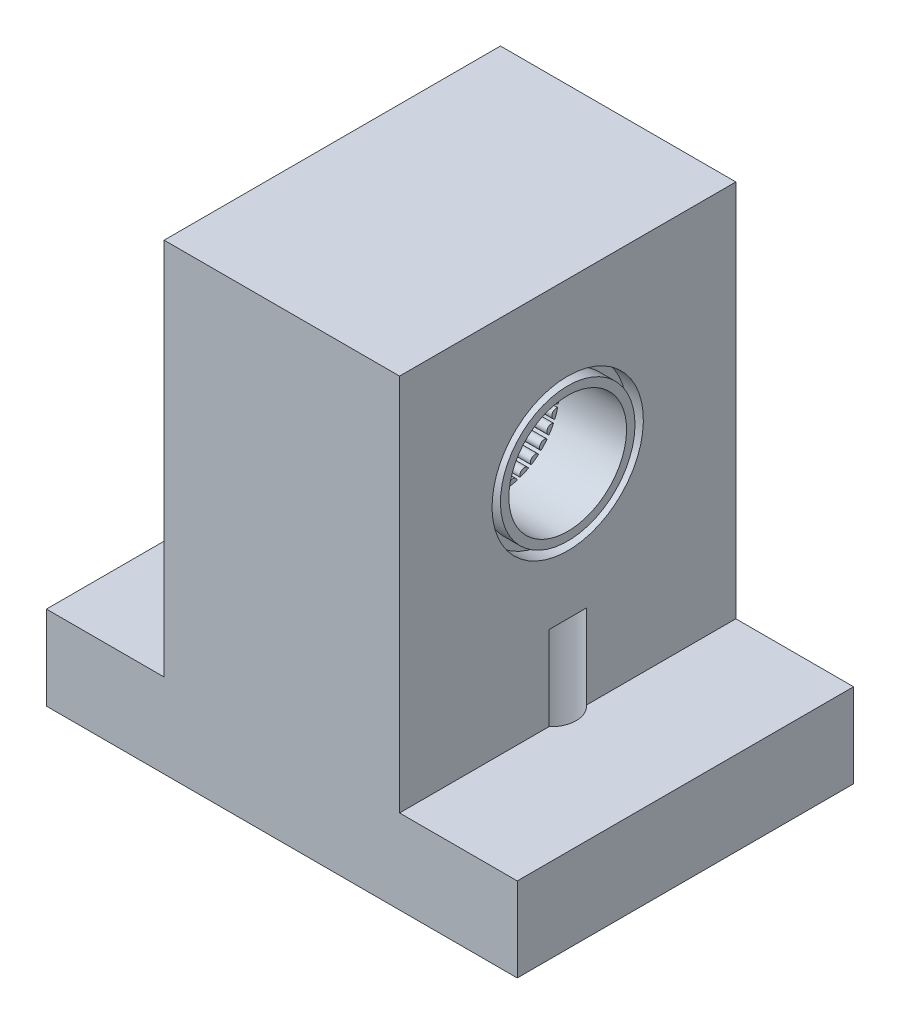
SolidWorks part; units mm, degrees
ref_plane "Alzado" through (0, 0, 0) normal (0, 0, 1) x (1, 0, 0)
ref_plane "Planta" through (0, 0, 0) normal (0, 1, 0) x (1, 0, 0)
ref_plane "Vista lateral" through (0, 0, 0) normal (1, 0, 0) x (0, 0, -1)
sketch "Croquis1" plane through (0, 0, 0) normal (0, 0, 1) x (1, 0, 0)
  line L0 (7, 13.75) -> (-7, 13.75)
  line L1 (-7, 13.75) -> (-7, -8.75)
  line L2 (-7, -8.75) -> (-14, -8.75)
  line L3 (-14, -8.75) -> (-14, -13.75)
  line L4 (-14, -13.75) -> (14, -13.75)
  line L5 (0, -13.75) -> (0, 13.75)
  line L6 (0, 28.2693) -> (0, -29.9167) construction
  line L7 (14, -8.75) -> (14, -13.75)
  line L8 (7, -8.75) -> (14, -8.75)
  line L9 (7, 13.75) -> (7, -8.75)
  point P10 (0, 0)
  dimension "D1" = 27.5
  dimension "D2" = 7
  dimension "D3" = 14
  dimension "D4" = 5
extrude "Saliente-Extruir1" add sketch "Croquis1" along normal mid plane 20 contours L9 L0 L5 L4 L7 L8 | L4 L5 L0 L1 L2 L3 region at (4.5769, -1.7308, 0) region at (-4.5769, -1.7308, 0)
sketch "Croquis4" plane through (7, 0, 0) normal (1, 0, 0) x (0, 0, -1)
  line L0 (0, 12.8173) -> (0, -5.1206) construction
  line L1 (-10, -13.75) -> (10, -13.75) construction
  circle A0 centre (0, 4.25) radius 3.5
  dimension "D2" = 7
  dimension "D1" = 18
extrude "Cortar-Extruir3" cut sketch "Croquis4" against normal blind 15
sketch "Croquis5" plane through (0, -13.75, 0) normal (0, -1, 0) x (1, 0, 0)
  line L0 (12.601, 0) -> (-13.2445, 0) construction
  line L1 (0, 4.0216) -> (0, -6.2022) construction
  circle A0 centre (-6, 0) radius 1.5
  circle A1 centre (6, 0) radius 1.5
  dimension "D1" = 3
  dimension "D2" = 6
extrude "Cortar-Extruir4" cut sketch "Croquis5" against normal blind 10
sketch "Croquis6" plane through (0, 0, 0) normal (1, 0, 0) x (0, 0, -1)
  line L0 (0, 7.75) -> (0, 0) construction
  circle A0 centre (0, 4.25) radius 3.5 construction
  arc A1 (0.2748, 7.7392) -> (-0.2748, 7.7392) centre (0, 4.25) ccw
  circle A2 centre (0, 4.25) radius 3.225 construction
  arc A3 (-0.2748, 7.7392) -> (0.2748, 7.7392) centre (0, 7.75) ccw
  arc A4 (0.9942, 7.6058) -> (0.4567, 7.7201) centre (0, 4.25) ccw
  arc A5 (0.4567, 7.7201) -> (0.9942, 7.6058) centre (0.7277, 7.6735) ccw
  arc A6 (1.6702, 7.3258) -> (1.1682, 7.5493) centre (0, 4.25) ccw
  arc A7 (1.1682, 7.5493) -> (1.6702, 7.3258) centre (1.4236, 7.4474) ccw
  arc A8 (2.2732, 6.9113) -> (1.8286, 7.2343) centre (0, 4.25) ccw
  arc A9 (1.8286, 7.2343) -> (2.2732, 6.9113) centre (2.0572, 7.0816) ccw
  arc A10 (2.7768, 6.3805) -> (2.4091, 6.7889) centre (0, 4.25) ccw
  arc A11 (2.4091, 6.7889) -> (2.7768, 6.3805) centre (2.601, 6.592) ccw
  arc A12 (3.1591, 5.7566) -> (2.8843, 6.2326) centre (0, 4.25) ccw
  arc A13 (2.8843, 6.2326) -> (3.1591, 5.7566) centre (3.0311, 6) ccw
  arc A14 (3.4033, 5.0669) -> (3.2335, 5.5896) centre (0, 4.25) ccw
  arc A15 (3.2335, 5.5896) -> (3.4033, 5.0669) centre (3.3287, 5.3316) ccw
  arc A16 (3.4988, 4.3414) -> (3.4414, 4.888) centre (0, 4.25) ccw
  arc A17 (3.4414, 4.888) -> (3.4988, 4.3414) centre (3.4808, 4.6158) ccw
  arc A18 (3.4414, 3.612) -> (3.4988, 4.1586) centre (0, 4.25) ccw
  arc A19 (3.4988, 4.1586) -> (3.4414, 3.612) centre (3.4808, 3.8842) ccw
  arc A20 (3.2335, 2.9104) -> (3.4033, 3.4331) centre (0, 4.25) ccw
  arc A21 (3.4033, 3.4331) -> (3.2335, 2.9104) centre (3.3287, 3.1684) ccw
  arc A22 (2.8843, 2.2674) -> (3.1591, 2.7434) centre (0, 4.25) ccw
  arc A23 (3.1591, 2.7434) -> (2.8843, 2.2674) centre (3.0311, 2.5) ccw
  arc A24 (2.4091, 1.7111) -> (2.7768, 2.1195) centre (0, 4.25) ccw
  arc A25 (2.7768, 2.1195) -> (2.4091, 1.7111) centre (2.601, 1.908) ccw
  arc A26 (1.8286, 1.2657) -> (2.2732, 1.5887) centre (0, 4.25) ccw
  arc A27 (2.2732, 1.5887) -> (1.8286, 1.2657) centre (2.0572, 1.4184) ccw
  arc A28 (1.1682, 0.9507) -> (1.6702, 1.1742) centre (0, 4.25) ccw
  arc A29 (1.6702, 1.1742) -> (1.1682, 0.9507) centre (1.4236, 1.0526) ccw
  arc A30 (0.4567, 0.7799) -> (0.9942, 0.8942) centre (0, 4.25) ccw
  arc A31 (0.9942, 0.8942) -> (0.4567, 0.7799) centre (0.7277, 0.8265) ccw
  arc A32 (-0.2748, 0.7608) -> (0.2748, 0.7608) centre (0, 4.25) ccw
  arc A33 (0.2748, 0.7608) -> (-0.2748, 0.7608) centre (0, 0.75) ccw
  arc A34 (-0.9942, 0.8942) -> (-0.4567, 0.7799) centre (0, 4.25) ccw
  arc A35 (-0.4567, 0.7799) -> (-0.9942, 0.8942) centre (-0.7277, 0.8265) ccw
  arc A36 (-1.6702, 1.1742) -> (-1.1682, 0.9507) centre (0, 4.25) ccw
  arc A37 (-1.1682, 0.9507) -> (-1.6702, 1.1742) centre (-1.4236, 1.0526) ccw
  arc A38 (-2.2732, 1.5887) -> (-1.8286, 1.2657) centre (0, 4.25) ccw
  arc A39 (-1.8286, 1.2657) -> (-2.2732, 1.5887) centre (-2.0572, 1.4184) ccw
  arc A40 (-2.7768, 2.1195) -> (-2.4091, 1.7111) centre (0, 4.25) ccw
  arc A41 (-2.4091, 1.7111) -> (-2.7768, 2.1195) centre (-2.601, 1.908) ccw
  arc A42 (-3.1591, 2.7434) -> (-2.8843, 2.2674) centre (0, 4.25) ccw
  arc A43 (-2.8843, 2.2674) -> (-3.1591, 2.7434) centre (-3.0311, 2.5) ccw
  arc A44 (-3.4033, 3.4331) -> (-3.2335, 2.9104) centre (0, 4.25) ccw
  arc A45 (-3.2335, 2.9104) -> (-3.4033, 3.4331) centre (-3.3287, 3.1684) ccw
  arc A46 (-3.4988, 4.1586) -> (-3.4414, 3.612) centre (0, 4.25) ccw
  arc A47 (-3.4414, 3.612) -> (-3.4988, 4.1586) centre (-3.4808, 3.8842) ccw
  arc A48 (-3.4414, 4.888) -> (-3.4988, 4.3414) centre (0, 4.25) ccw
  arc A49 (-3.4988, 4.3414) -> (-3.4414, 4.888) centre (-3.4808, 4.6158) ccw
  arc A50 (-3.2335, 5.5896) -> (-3.4033, 5.0669) centre (0, 4.25) ccw
  arc A51 (-3.4033, 5.0669) -> (-3.2335, 5.5896) centre (-3.3287, 5.3316) ccw
  arc A52 (-2.8843, 6.2326) -> (-3.1591, 5.7566) centre (0, 4.25) ccw
  arc A53 (-3.1591, 5.7566) -> (-2.8843, 6.2326) centre (-3.0311, 6) ccw
  arc A54 (-2.4091, 6.7889) -> (-2.7768, 6.3805) centre (0, 4.25) ccw
  arc A55 (-2.7768, 6.3805) -> (-2.4091, 6.7889) centre (-2.601, 6.592) ccw
  arc A56 (-1.8286, 7.2343) -> (-2.2732, 6.9113) centre (0, 4.25) ccw
  arc A57 (-2.2732, 6.9113) -> (-1.8286, 7.2343) centre (-2.0572, 7.0816) ccw
  arc A58 (-1.1682, 7.5493) -> (-1.6702, 7.3258) centre (0, 4.25) ccw
  arc A59 (-1.6702, 7.3258) -> (-1.1682, 7.5493) centre (-1.4236, 7.4474) ccw
  arc A60 (-0.4567, 7.7201) -> (-0.9942, 7.6058) centre (0, 4.25) ccw
  arc A61 (-0.9942, 7.6058) -> (-0.4567, 7.7201) centre (-0.7277, 7.6735) ccw
  point P10 (0, 7.475)
  dimension "D1" = 6.45
  dimension "D2" = 30
extrude "Saliente-Extruir2" add sketch "Croquis6" along normal blind 3 and the other way blind 3
sketch "Croquis7" plane through (7, 0, 0) normal (1, 0, 0) x (0, 0, -1)
  line L0 (-10, -13.75) -> (10, -13.75) construction
  line L1 (0, 12.4669) -> (0, -5.7544) construction
  circle A0 centre (0, 4.25) radius 4
  circle A1 centre (0, 4.25) radius 4.5
  dimension "D2" = 8
  dimension "D1" = 18
  dimension "D3" = 0.5
extrude "Cortar-Extruir5" cut sketch "Croquis7" against normal blind 1
mirror "Simetría1" about plane through (0, 0, 0) normal (1, 0, 0) of "Cortar-Extruir5"
